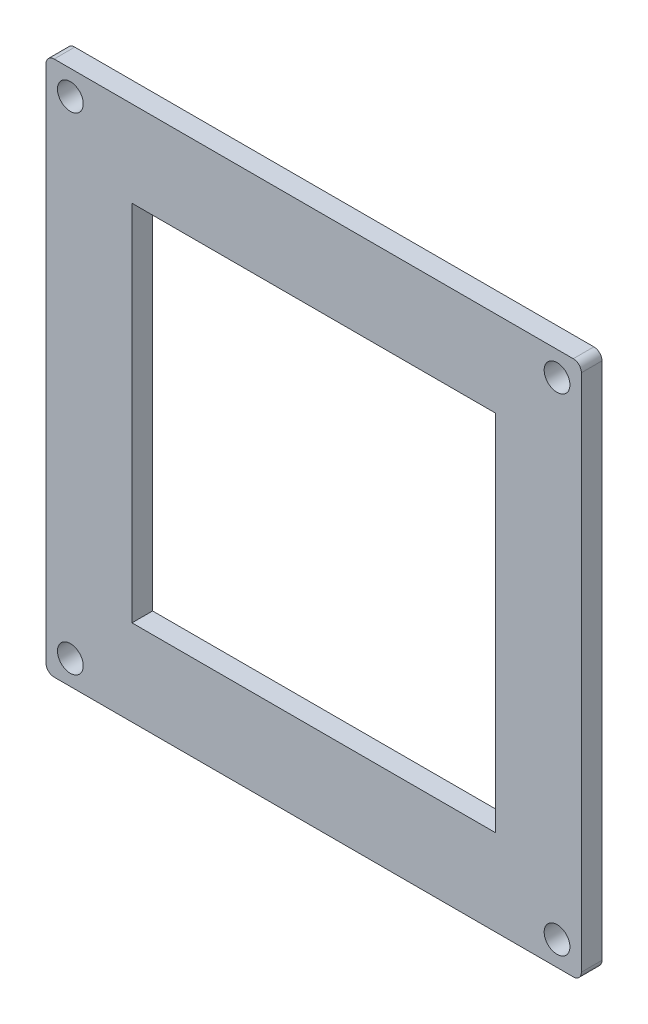
SolidWorks part; units mm, degrees
ref_plane "Front Plane" through (0, 0, 0) normal (0, 0, 1) x (1, 0, 0)
ref_plane "Top Plane" through (0, 0, 0) normal (0, 1, 0) x (1, 0, 0)
ref_plane "Right Plane" through (0, 0, 0) normal (1, 0, 0) x (0, 0, -1)
sketch "Sketch1" plane through (0, 0, 0) normal (0, 0, 1) x (1, 0, 0)
  line L1 (-30, 30) -> (30, 30) construction
  line L2 (-30, 30) -> (-30, -30) construction
  line L3 (-30, -30) -> (30, -30) construction
  line L4 (30, 30) -> (30, -30) construction
  line L5 (0, -30) -> (0, 30) construction
  line L6 (-30, 0) -> (30, 0) construction
  line L7 (-33, 33) -> (33, 33)
  line L8 (-33, 33) -> (-33, -33)
  line L9 (-33, -33) -> (33, -33)
  line L10 (33, 33) -> (33, -33)
  line L11 (0, -33) -> (0, 33) construction
  line L12 (-33, 0) -> (33, 0) construction
  line L13 (-22.4, 22.4) -> (22.4, 22.4)
  line L14 (-22.4, 22.4) -> (-22.4, -22.4)
  line L15 (-22.4, -22.4) -> (22.4, -22.4)
  line L16 (22.4, 22.4) -> (22.4, -22.4)
  line L17 (0, -22.4) -> (0, 22.4) construction
  line L18 (-22.4, 0) -> (22.4, 0) construction
  circle A0 centre (30, 30) radius 1.59
  circle A1 centre (-30, 30) radius 1.59
  circle A2 centre (-30, -30) radius 1.59
  circle A3 centre (30, -30) radius 1.59
  point P0 (0, 0)
  point P4 (0, 0)
  point P8 (0, 0)
  dimension "D2" = 3.18
  dimension "D1" = 60
  dimension "D3" = 44.8
  dimension "D4" = 66
extrude "Boss-Extrude1" add sketch "Sketch1" along normal blind 2.54
fillet "Fillet1" radius 1 4 edges at (-33, 33, 1.27) (-33, -33, 1.27) (33, -33, 1.27) (33, 33, 1.27)
equation "\"D3@Sketch1\"=50.8 - 3*2"
